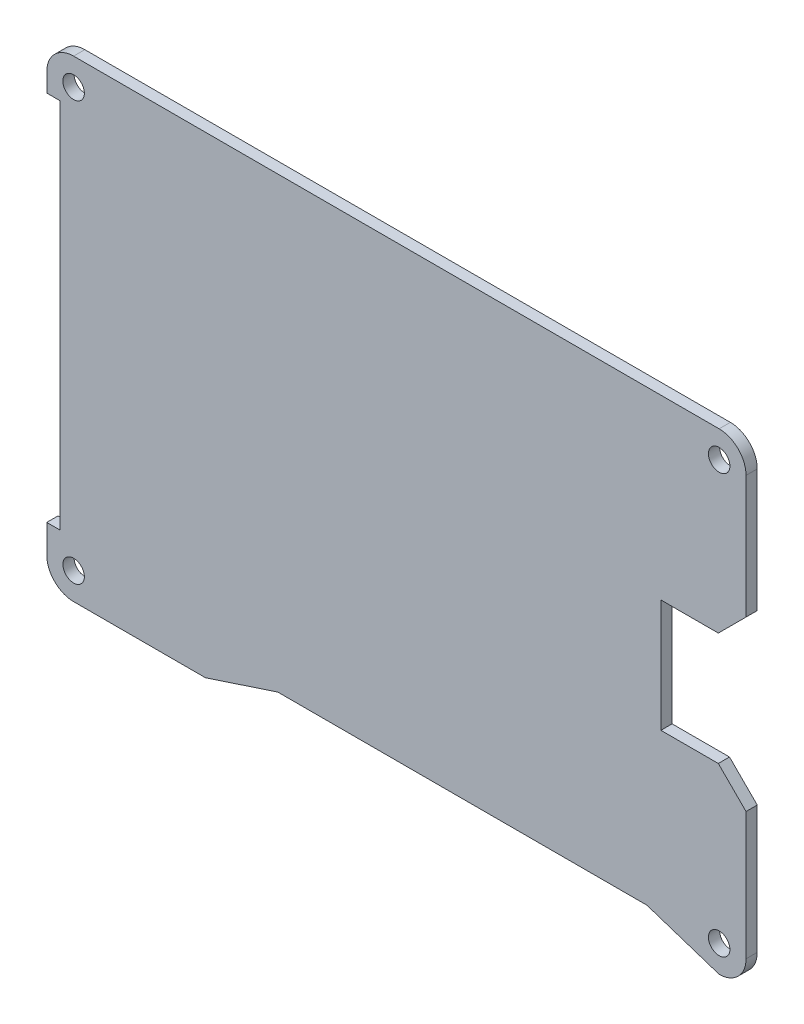
SolidWorks part; units mm, degrees
ref_plane "Front Plane" through (0, 0, 0) normal (0, 0, 1) x (1, 0, 0)
ref_plane "Top Plane" through (0, 0, 0) normal (0, 1, 0) x (1, 0, 0)
ref_plane "Right Plane" through (0, 0, 0) normal (1, 0, 0) x (0, 0, -1)
sketch "Sketch1" plane through (0, 0, 0) normal (0, 0, 1) x (1, 0, 0)
  line L5 (-301.9473, 132.8157) -> (-301.9473, 150.9704) construction
  line L6 (-305.7573, 154.7804) -> (-397.2471, 154.7804) construction
  line L7 (-401.0571, 150.9566) -> (-401.0571, 148.341) construction
  line L8 (-401.0571, 148.341) -> (-399.1521, 148.341) construction
  line L9 (-399.1521, 148.341) -> (-399.1521, 95.6449) construction
  line L10 (-399.1521, 95.6449) -> (-401.0571, 95.6449) construction
  line L11 (-401.0571, 95.6449) -> (-401.0571, 91.6593) construction
  line L12 (-397.2472, 87.8217) -> (-378.5565, 87.8217) construction
  line L13 (-378.5565, 87.8217) -> (-368.3165, 91.1883) construction
  line L14 (-368.3165, 91.1883) -> (-315.9973, 91.1883) construction
  line L15 (-315.9973, 91.1883) -> (-305.7573, 87.8217) construction
  line L16 (-301.9473, 91.6317) -> (-301.9473, 111.7465) construction
  line L17 (-301.9473, 133.5777) -> (-305.878, 129.6471)
  line L18 (-305.878, 129.6471) -> (-314.0123, 129.6471)
  line L19 (-314.0123, 129.6471) -> (-314.0123, 113.6451)
  line L20 (-314.0123, 113.6451) -> (-305.8779, 113.6451)
  line L21 (-305.8779, 113.6451) -> (-301.9473, 109.7145)
  line L22 (-301.9473, 133.5777) -> (-301.9473, 150.9704)
  line L23 (-305.7573, 154.7804) -> (-397.2471, 154.7804)
  line L24 (-401.0571, 150.9566) -> (-401.0571, 148.341)
  line L25 (-401.0571, 148.341) -> (-399.1521, 148.341)
  line L26 (-399.1521, 148.341) -> (-399.1521, 95.6449)
  line L27 (-399.1521, 95.6449) -> (-401.0571, 95.6449)
  line L28 (-401.0571, 95.6449) -> (-401.0571, 91.6593)
  line L29 (-397.2472, 87.8217) -> (-378.5565, 87.8217)
  line L30 (-378.5565, 87.8217) -> (-368.3165, 91.1883)
  line L31 (-368.3165, 91.1883) -> (-315.9973, 91.1883)
  line L32 (-315.9973, 91.1883) -> (-305.7573, 87.8217)
  line L33 (-301.9473, 91.6317) -> (-301.9473, 109.7145)
  circle A4 centre (-305.7573, 150.9704) radius 1.524
  circle A5 centre (-397.2471, 150.9704) radius 1.524
  circle A6 centre (-397.2472, 91.6317) radius 1.524
  circle A7 centre (-305.7573, 91.6317) radius 1.524
  arc A8 (-301.9473, 150.9704) -> (-305.7573, 154.7804) centre (-305.7573, 150.9704) ccw construction
  arc A9 (-397.2471, 154.7804) -> (-401.0571, 150.9566) centre (-397.2471, 150.9704) ccw construction
  arc A10 (-401.0571, 91.6593) -> (-397.2472, 87.8217) centre (-397.2472, 91.6317) ccw construction
  arc A11 (-305.7573, 87.8217) -> (-301.9473, 91.6317) centre (-305.7573, 91.6317) ccw construction
  arc A12 (-301.9473, 150.9704) -> (-305.7573, 154.7804) centre (-305.7573, 150.9704) ccw
  arc A13 (-397.2471, 154.7804) -> (-401.0571, 150.9566) centre (-397.2471, 150.9704) ccw
  arc A14 (-401.0571, 91.6593) -> (-397.2472, 87.8217) centre (-397.2472, 91.6317) ccw
  arc A15 (-305.7573, 87.8217) -> (-301.9473, 91.6317) centre (-305.7573, 91.6317) ccw
  dimension "D7" = 3.048
  dimension "D1" = 17.3927
  dimension "D2" = 3.9306
  dimension "D3" = 16.002
  dimension "D4" = 3.9307
  dimension "D5" = 8.1343
  dimension "D6" = 3.9307
extrude "Boss-Extrude1" add sketch "Sketch1" along normal blind 1.5875
sketch "Sketch2" [suppressed] plane through (0, 0, 1.5875) normal (0, 0, 1) x (1, 0, 0)
  line L0 (-351.5022, 121.301) -> (-351.5022, 159.401) construction
  line L1 (-301.9473, 150.9704) -> (-301.9473, 91.6317) construction
  line L2 (-401.0571, 121.301) -> (-301.9473, 121.301) construction
  line L3 (-351.5022, 83.201) -> (-351.5022, 159.401) construction
  line L4 (-361.0272, 83.201) -> (-361.0272, 159.401)
  line L5 (-341.9772, 83.201) -> (-341.9772, 159.401)
  line L6 (-361.0272, 154.7804) -> (-341.9772, 154.7804)
  line L7 (-305.7573, 154.7804) -> (-397.2471, 154.7804) construction
  line L8 (-361.0272, 91.6317) -> (-341.9772, 91.6317)
  circle A0 centre (-351.5022, 159.401) radius 3.175
  arc A1 (-361.0272, 83.201) -> (-341.9772, 83.201) centre (-351.5022, 83.201) ccw
  arc A2 (-341.9772, 159.401) -> (-361.0272, 159.401) centre (-351.5022, 159.401) ccw
  circle A3 centre (-351.5022, 83.201) radius 3.175
  point P13 (-351.5022, 121.301)
  line M11 (-305.7573, 154.7804) -> (-397.2471, 154.7804)
  line M21 (-368.3165, 91.1883) -> (-315.9973, 91.1883)
  dimension "D1" = 6.35
  dimension "D2" = 38.1
  dimension "D3" = 19.05
extrude "Boss-Extrude2" [suppressed] add sketch "Sketch2" against normal blind 1.5875 contours L5 A2 L4 A0 M11 | L4 A1 L5 A3 M21
sketch "Sketch6" [suppressed] plane through (0, 0, 1.5875) normal (0, 0, 1) x (1, 0, 0)
  line L0 (-386.6812, 159.8604) -> (-386.6812, 154.7804)
  line L1 (-305.7573, 154.7804) -> (-397.2471, 154.7804) construction
  line L2 (-379.8232, 159.8604) -> (-379.8232, 154.7804)
  line L3 (-379.8232, 154.7804) -> (-386.6812, 154.7804)
  line L4 (-316.3232, 159.8604) -> (-316.3232, 154.7804)
  line L5 (-316.3232, 154.7804) -> (-323.1812, 154.7804)
  line L6 (-323.1812, 154.7804) -> (-323.1812, 159.8604)
  line L7 (-383.2522, 159.8604) -> (-319.7522, 159.8604) construction
  line L8 (-351.5022, 159.8604) -> (-351.5022, 154.7804) construction
  line L10 (-351.5022, 154.7804) -> (-351.5022, 91.1883) construction
  line L11 (-368.3165, 91.1883) -> (-315.9973, 91.1883) construction
  line L12 (-361.2812, 83.5683) -> (-361.2812, 91.1883)
  line L13 (-361.2812, 91.1883) -> (-354.4232, 91.1883)
  line L14 (-354.4232, 91.1883) -> (-354.4232, 83.5683)
  circle A0 centre (-383.2522, 159.8604) radius 1.7843
  circle A1 centre (-319.7522, 159.8604) radius 1.7843
  circle A2 centre (-383.2522, 159.8604) radius 3.429
  circle A3 centre (-319.7522, 159.8604) radius 3.429
  circle A4 centre (-357.8522, 83.5683) radius 1.7145
  circle A5 centre (-357.8522, 83.5683) radius 3.429
  line M7 (-305.7573, 154.7804) -> (-397.2471, 154.7804)
  line M17 (-368.3165, 91.1883) -> (-315.9973, 91.1883)
  dimension "D2" = 6.858
  dimension "D3" = 3.5687
  dimension "D4" = 5.08
  dimension "D5" = 6.858
  dimension "D6" = 3.429
  dimension "D7" = 7.62
  dimension "D1" = 63.5
  dimension "D8" = 38.1
extrude "Boss-Extrude4" [suppressed] add sketch "Sketch6" against normal up to vertex contours A2 A0 | A2 L0 L2 M7 | A3 L6 L4 M7 | A3 A1 | A5 A4 | A5 L14 L12 M17 up to point (-368.3165, 91.1883, 0)
sketch "Sketch7" plane through (0, 0, 1.5875) normal (0, 0, 1) x (1, 0, 0)
  line L0 (-351.5022, 154.7804) -> (-351.5022, 91.1883) construction
  line L1 (-305.7573, 154.7804) -> (-397.2471, 154.7804) construction
  line L2 (-368.3165, 91.1883) -> (-315.9973, 91.1883) construction
  line L3 (-383.2522, 159.8604) -> (-319.7522, 159.8604) construction
  line L4 (-351.5022, 159.8604) -> (-351.5022, 154.7804) construction
  line L5 (-386.6812, 159.8604) -> (-386.6812, 154.7804)
  line L6 (-386.6812, 154.7804) -> (-379.8232, 154.7804)
  line L7 (-379.8232, 154.7804) -> (-379.8232, 159.8604)
  line L8 (-323.1812, 159.8604) -> (-323.1812, 154.7804)
  line L9 (-323.1812, 154.7804) -> (-316.3232, 154.7804)
  line L10 (-316.3232, 154.7804) -> (-316.3232, 159.8604)
  line L11 (-354.9312, 83.6604) -> (-354.9312, 91.1883)
  line L12 (-354.9312, 91.1883) -> (-348.0732, 91.1883)
  line L13 (-348.0732, 91.1883) -> (-348.0732, 83.6604)
  circle A0 centre (-383.2522, 159.8604) radius 1.7843
  circle A1 centre (-319.7522, 159.8604) radius 1.7843
  circle A2 centre (-383.2522, 159.8604) radius 3.429
  circle A3 centre (-319.7522, 159.8604) radius 3.429
  circle A4 centre (-351.5022, 83.6604) radius 1.7843
  circle A5 centre (-351.5022, 83.6604) radius 3.429
  line M5 (-305.7573, 154.7804) -> (-397.2471, 154.7804)
  line M15 (-368.3165, 91.1883) -> (-315.9973, 91.1883)
  dimension "D1" = 3.5687
  dimension "D3" = 6.858
  dimension "D2" = 63.5
  dimension "D4" = 5.08
  dimension "D5" = 76.2
extrude "Boss-Extrude5" [suppressed] add sketch "Sketch7" against normal up to vertex contours A2 L5 L7 M5 | A2 A0 | A3 L8 L10 M5 | A3 A1 | A5 A4 | A5 L13 L11 M15 up to point (-315.9973, 91.1883, 0)
